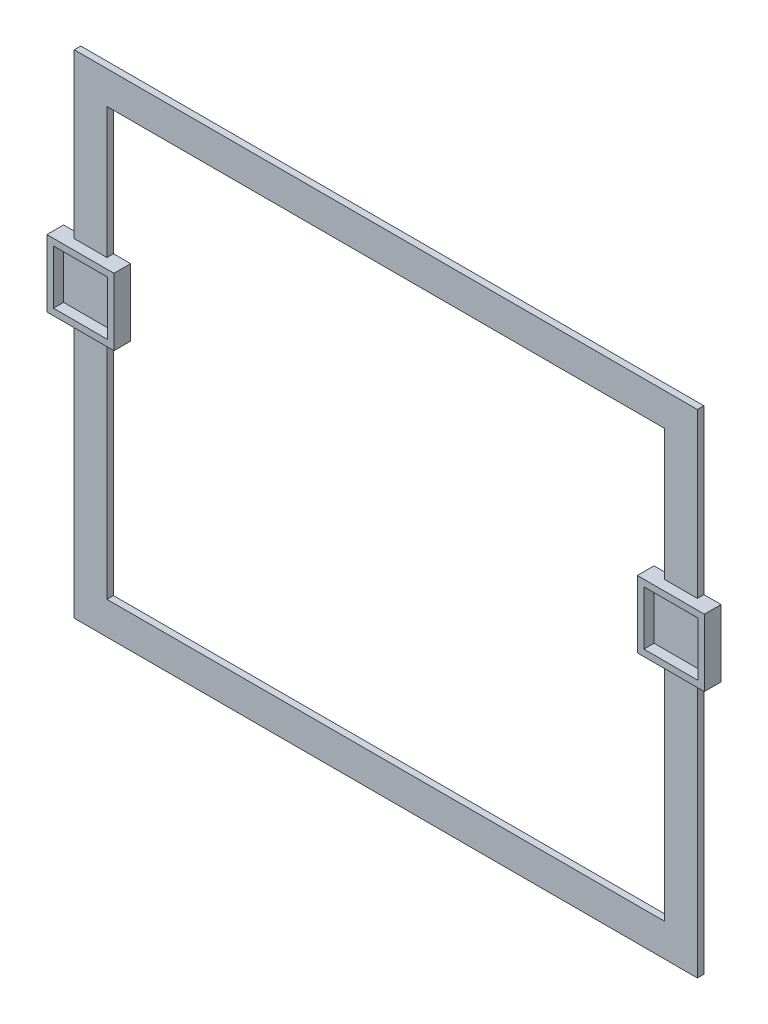
SolidWorks part; units mm, degrees
ref_plane "Front Plane" through (0, 0, 0) normal (0, 0, 1) x (1, 0, 0)
ref_plane "Top Plane" through (0, 0, 0) normal (0, 1, 0) x (1, 0, 0)
ref_plane "Right Plane" through (0, 0, 0) normal (1, 0, 0) x (0, 0, -1)
sketch "Sketch1" plane through (0, 0, 0) normal (0, 0, 1) x (1, 0, 0)
  line L1 (0, 0) -> (41.91, 0)
  line L2 (0, 0) -> (0, 41.91)
  line L3 (0, 41.91) -> (41.91, 41.91)
  line L4 (41.91, 0) -> (41.91, 41.91)
  line L5 (-5.08, 46.99) -> (46.99, 46.99)
  line L6 (-5.08, 46.99) -> (-5.08, -5.08)
  line L7 (-5.08, -5.08) -> (46.99, -5.08)
  line L8 (46.99, 46.99) -> (46.99, -5.08)
  line L9 (458.47, 41.91) -> (500.38, 41.91)
  line L10 (458.47, 41.91) -> (458.47, 0)
  line L11 (458.47, 0) -> (500.38, 0)
  line L12 (500.38, 41.91) -> (500.38, 0)
  line L13 (453.39, 46.99) -> (505.46, 46.99)
  line L14 (453.39, 46.99) -> (453.39, -5.08)
  line L15 (453.39, -5.08) -> (505.46, -5.08)
  line L16 (505.46, 46.99) -> (505.46, -5.08)
  point P17 (458.47, 20.955)
  dimension "D1" = 41.91
  dimension "D2" = 41.91
  dimension "D3" = 5.08
  dimension "D4" = 5.08
  dimension "D5" = 5.08
  dimension "D6" = 5.08
  dimension "D7" = 41.91
  dimension "D8" = 41.91
  dimension "D9" = 5.08
  dimension "D10" = 5.08
  dimension "D11" = 406.4
extrude "Boss-Extrude1" add sketch "Sketch1" along normal blind 7.874
sketch "Sketch2" plane through (0, 0, 0) normal (0, 0, -1) x (-1, 0, 0)
  line L0 (-46.99, 46.99) -> (5.08, 46.99) construction
  line L10 (-8.255, -5.08) -> (-8.255, -208.28)
  line L11 (-8.255, -208.28) -> (-33.655, -208.28)
  line L12 (-33.655, -5.08) -> (-33.655, -182.88)
  line L15 (-365.125, -208.28) -> (-390.525, -208.28)
  line L25 (-33.655, -208.28) -> (-365.125, -208.28)
  line L27 (-33.655, -182.88) -> (-365.125, -182.88)
  line L34 (-8.255, 46.99) -> (-8.255, 173.99)
  line L35 (-8.255, 173.99) -> (-33.655, 173.99)
  line L37 (-46.99, -5.08) -> (-46.99, 46.99) construction
  line L40 (-365.125, 173.99) -> (-391.5985, 173.99)
  line L54 (-33.655, 173.99) -> (-365.125, 173.99)
  line L55 (-33.655, 46.99) -> (-33.655, 148.59)
  line L56 (-33.655, 148.59) -> (-33.655, 46.99)
  line L57 (-466.725, 46.99) -> (-466.725, 148.59)
  line L58 (-365.125, 148.59) -> (-33.655, 148.59)
  line L59 (-505.46, 46.99) -> (-453.39, 46.99) construction
  line L61 (-8.255, 46.99) -> (-33.655, 46.99)
  line L62 (-8.255, -5.08) -> (-33.655, -5.08)
  line L63 (5.08, -5.08) -> (-46.99, -5.08) construction
  line L64 (-466.725, 148.59) -> (-365.125, 148.59)
  line L65 (-453.39, 46.99) -> (-453.39, -5.08) construction
  line L67 (-492.125, 46.99) -> (-492.125, 173.99)
  line L68 (-492.125, 173.99) -> (-391.5985, 173.99)
  line L69 (-466.725, 46.99) -> (-492.125, 46.99)
  line L70 (-466.725, -5.08) -> (-466.725, -182.88)
  line L71 (-453.39, -5.08) -> (-505.46, -5.08) construction
  line L72 (-466.725, -182.88) -> (-365.125, -182.88)
  line L73 (-492.125, -5.08) -> (-492.125, -208.28)
  line L74 (-492.125, -208.28) -> (-390.525, -208.28)
  line L75 (-466.725, -5.08) -> (-492.125, -5.08)
  line M48 (5.08, 46.99) -> (-46.99, 46.99)
  line M50 (-46.99, -5.08) -> (5.08, -5.08)
  dimension "D1" = 203.2
  dimension "D2" = 25.4
  dimension "D3" = 127
  dimension "D4" = 25.4
  dimension "D5" = 13.335
  dimension "D6" = 101.6
  dimension "D7" = 0
  dimension "D8" = 25.4
  dimension "D9" = 25.4
  dimension "D10" = 331.47
  dimension "D11" = 127
  dimension "D12" = 25.4
  dimension "D13" = 13.335
extrude "Boss-Extrude3" add sketch "Sketch2" along normal blind 5.08 separate body contours L58 L55 L34 L35 L54 L40 M48 | L15 L25 L11 L10 L12 L27 M50 region at (13.5031, -106.68, 0) region at (20.955, 51.9926, 0)
sketch "Sketch3" plane through (0, 0, 0) normal (0, 0, -1) x (-1, 0, 0)
  line L1 (5.08, -5.08) -> (-46.99, -5.08)
  line L2 (5.08, -5.08) -> (5.08, 46.99)
  line L3 (5.08, 46.99) -> (-46.99, 46.99)
  line L4 (-46.99, -5.08) -> (-46.99, 46.99)
  line L5 (-453.39, -5.08) -> (-505.46, -5.08)
  line L6 (-453.39, -5.08) -> (-453.39, 46.99)
  line L7 (-453.39, 46.99) -> (-505.46, 46.99)
  line L8 (-505.46, -5.08) -> (-505.46, 46.99)
extrude "Boss-Extrude4" add sketch "Sketch3" along normal blind 5.08
